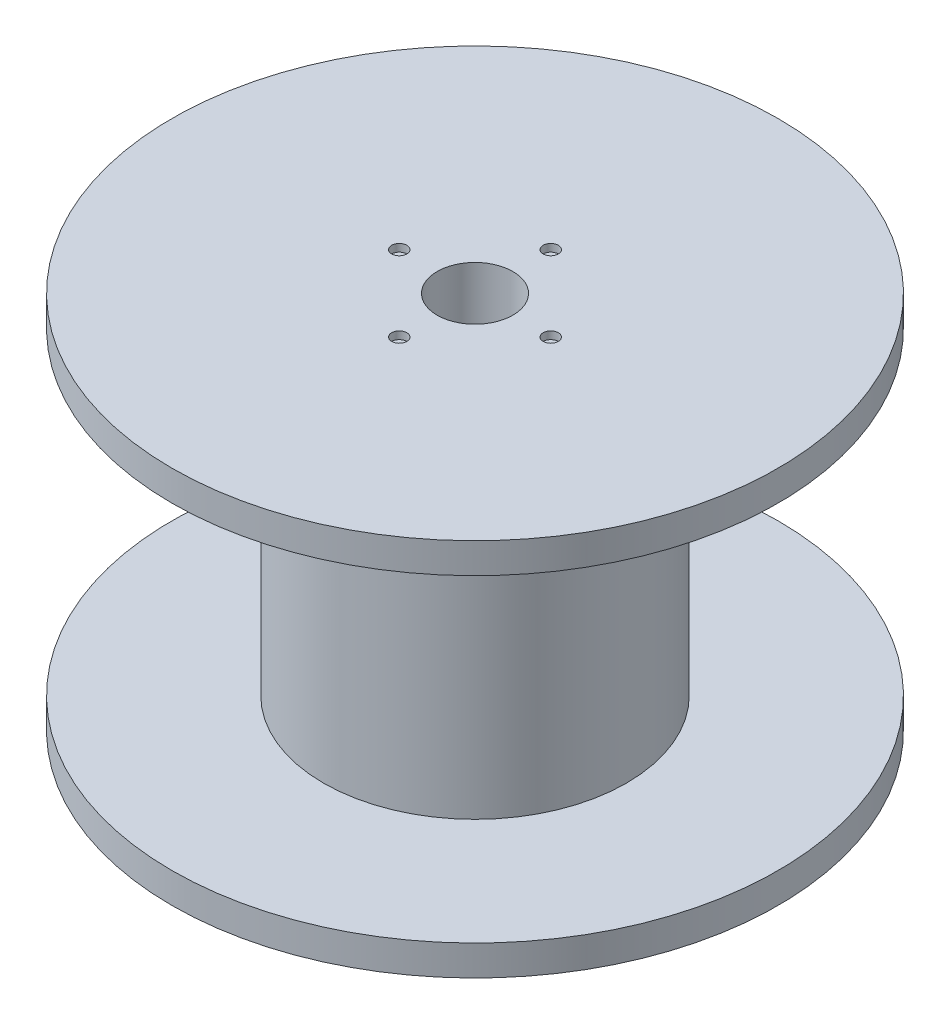
SolidWorks part; units mm, degrees
material "ABS"
ref_plane "Alzado" through (0, 0, 0) normal (0, 0, 1) x (1, 0, 0)
ref_plane "Planta" through (0, 0, 0) normal (0, 1, 0) x (1, 0, 0)
ref_plane "Vista lateral" through (0, 0, 0) normal (1, 0, 0) x (0, 0, -1)
sketch "Croquis1" plane through (0, 0, 0) normal (0, 1, 0) x (1, 0, 0)
  circle A0 centre (0, 0) radius 10
  dimension "D1" = 20
extrude "Saliente-Extruir1" add sketch "Croquis1" along normal blind 25
sketch "Croquis2" plane through (0, 25, 0) normal (0, 1, 0) x (1, 0, 0)
  circle A0 centre (0, 0) radius 20
  dimension "D1" = 40
extrude "Saliente-Extruir2" add sketch "Croquis2" against normal blind 2
extrude "Saliente-Extruir3" add sketch "Croquis2<2>" along normal blind 2 from offset 25 offset against normal yes
sketch "Croquis2<2>" plane through (0, 25, 0) normal (0, 1, 0) x (1, 0, 0) same geometry as "Croquis2"
sketch "Croquis3" plane through (0, 25, 0) normal (0, 1, 0) x (1, 0, 0)
  circle A0 centre (0, 0) radius 2.5
  dimension "D1" = 5
extrude "Cortar-Extruir1" cut sketch "Croquis3" against normal through all
sketch "Croquis4" plane through (0, 25, 0) normal (0, 1, 0) x (1, 0, 0)
  circle A0 centre (0, 5) radius 0.5
  circle A1 centre (5, 0) radius 0.5
  circle A2 centre (0, -5) radius 0.5
  circle A3 centre (-5, 0) radius 0.5
  dimension "D1" = 1
  dimension "D2" = 5
  dimension "D3" = 5
  dimension "D4" = 5
  dimension "D5" = 5
extrude "Cortar-Extruir2" cut sketch "Croquis4" against normal blind 0.5
extrude "Cortar-Extruir3" cut sketch "Croquis4<2>" along normal blind 0.5 from offset 25 offset against normal yes
sketch "Croquis4<2>" plane through (0, 25, 0) normal (0, 1, 0) x (1, 0, 0) same geometry as "Croquis4"
